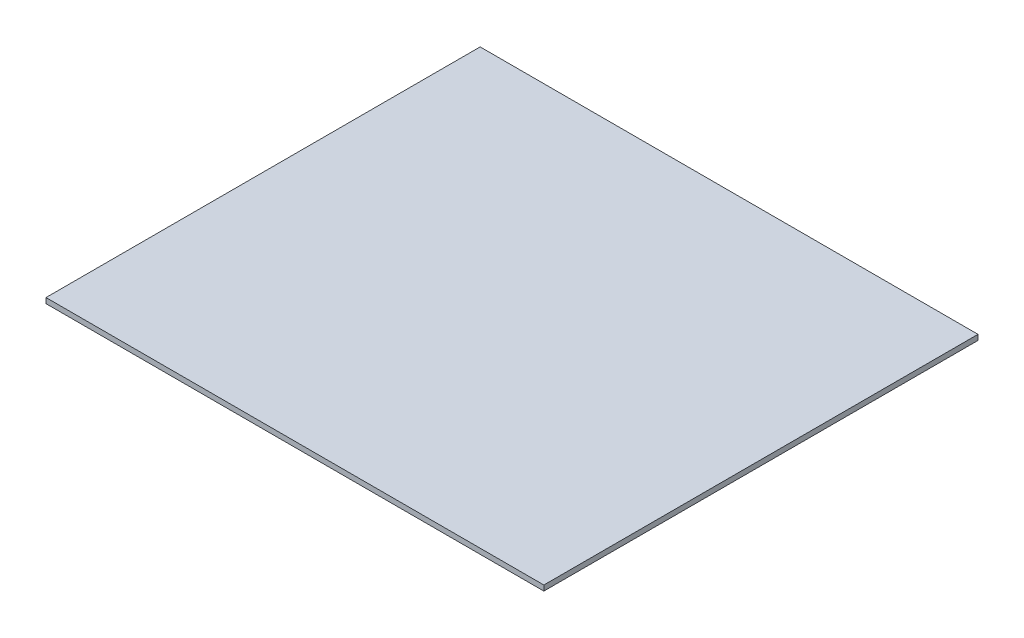
SolidWorks part; units mm, degrees
ref_plane "Front Plane" through (0, 0, 0) normal (0, 0, 1) x (1, 0, 0)
ref_plane "Top Plane" through (0, 0, 0) normal (0, 1, 0) x (1, 0, 0)
ref_plane "Right Plane" through (0, 0, 0) normal (1, 0, 0) x (0, 0, -1)
sketch "Sketch1" plane through (0, 0, 0) normal (0, 1, 0) x (1, 0, 0)
  line L1 (-17.3059, 508.2237) -> (578.0066, 508.2237)
  line L2 (-17.3059, 508.2237) -> (-17.3059, -10.8888)
  line L3 (-17.3059, -10.8888) -> (578.0066, -10.8888)
  line L4 (578.0066, 508.2237) -> (578.0066, -10.8888)
  dimension "D1" = 519.1125
  dimension "D2" = 595.3125
extrude "Boss-Extrude1" add sketch "Sketch1" along normal blind 6.35
